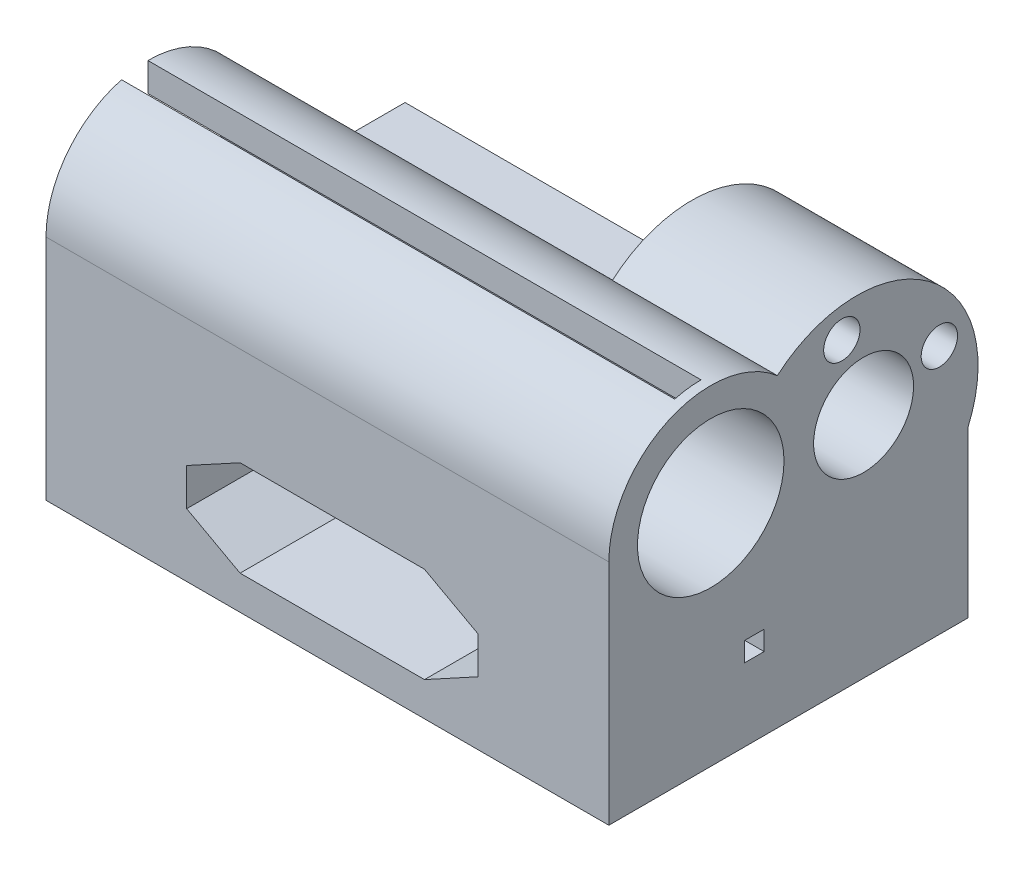
SolidWorks part; units mm, degrees
ref_plane "Front Plane" through (0, 0, 0) normal (0, 0, 1) x (1, 0, 0)
ref_plane "Top Plane" through (0, 0, 0) normal (0, 1, 0) x (1, 0, 0)
ref_plane "Right Plane" through (0, 0, 0) normal (1, 0, 0) x (0, 0, -1)
sketch "Sketch2" plane through (0, 0, 0) normal (0, 1, 0) x (1, 0, 0)
  line L1 (-29, -18.5) -> (29, -18.5)
  line L2 (-29, -18.5) -> (-29, 18.5)
  line L3 (-29, 18.5) -> (29, 18.5)
  line L4 (29, -18.5) -> (29, 18.5)
  line L5 (-29, -18.5) -> (29, 18.5) construction
  line L6 (-29, 18.5) -> (29, -18.5) construction
  point P0 (0, 0)
  dimension "D1" = 58
  dimension "D2" = 37
extrude "Boss-Extrude1" add sketch "Sketch2" along normal blind 17
sketch "Sketch3" plane through (29, 0, 0) normal (1, 0, 0) x (0, 0, -1)
  line L0 (-18.5, 0) -> (18.5, 0) construction
  line L1 (-18.5, 23.5) -> (-18.5, 17)
  line L2 (-18.5, 17) -> (-18.5, 0) construction
  line L5 (2.5, 23.5) -> (2.5, 17)
  line L6 (-18.5, 17) -> (18.5, 17) construction
  line L7 (-18.5, 17) -> (2.5, 17)
  arc A0 (2.5, 23.5) -> (-18.5, 23.5) centre (-8, 23.5) ccw
  dimension "D2" = 21
  dimension "D4" = 23.5
  dimension "D5" = 10.5
extrude "Boss-Extrude2" add sketch "Sketch3" against normal up to surface (58 mm away) up to face at (-29, 8.5, 0)
sketch "Sketch4" plane through (29, 0, 0) normal (1, 0, 0) x (0, 0, -1)
  line L1 (-18.5, 0) -> (18.5, 0) construction
  circle A0 centre (7.0436, 22) radius 12.5
  dimension "D1" = 25
  dimension "D2" = 22
extrude "Boss-Extrude3" add sketch "Sketch4" against normal blind 17
sketch "Sketch5" plane through (0, 0, -18.5) normal (0, 0, -1) x (-1, 0, 0)
  line L0 (-15.5, 6.5) -> (-15.5, 10.35)
  line L1 (-15.5, 10.35) -> (-10, 13.35)
  line L2 (-10, 13.35) -> (9, 13.35)
  line L3 (9, 13.35) -> (14.5, 10.357)
  line L4 (14.5, 10.357) -> (14.5, 6.5)
  line L5 (14.5, 6.5) -> (9, 3.5)
  line L6 (9, 3.5) -> (-10, 3.5)
  line L7 (-10, 3.5) -> (-15.5, 6.5)
  line L8 (-29, 0) -> (29, 0) construction
  line L9 (-29, 17) -> (-29, 0) construction
  line L10 (-23, 5.2045) -> (-23, 14.6536) construction
  line L11 (22, 4.2644) -> (22, 14.6536) construction
  line L12 (-23, 14.6536) -> (22, 14.6536) construction
  line L13 (-0.5, 14.6536) -> (-0.5, 7.909) construction
  line L14 (-29, 8.5) -> (29, 8.5) construction
  line L15 (29, 17) -> (29, 0) construction
  dimension "D1" = 3.85
  dimension "D2" = 3.857
  dimension "D3" = 3
  dimension "D4" = 3
  dimension "D5" = 5.5
  dimension "D6" = 5.5
  dimension "D8" = 5.5
  dimension "D9" = 19
  dimension "D10" = 3.5
  dimension "D11" = 15
  dimension "D12" = 6
  dimension "D13" = 45
extrude "Cut-Extrude1" cut sketch "Sketch5" against normal through all
sketch "Sketch6" plane through (0, 0, -18.5) normal (0, 0, -1) x (-1, 0, 0)
  line L0 (-29, 0) -> (29, 0) construction
  line L1 (-29, 17) -> (-29, 0) construction
  circle A0 centre (-23, 8.5) radius 4.076
  circle A1 centre (22, 8.5) radius 4.076
  dimension "D5" = 8.152
  dimension "D6" = 8.152
  dimension "D1" = 8.5
  dimension "D2" = 8.5
  dimension "D3" = 6
  dimension "D4" = 45
extrude "Cut-Extrude2" cut sketch "Sketch6" against normal blind 23
sketch "Sketch7" plane through (29, 0, 0) normal (1, 0, 0) x (0, 0, -1)
  line L0 (-18.5, 23.5) -> (-18.5, 0) construction
  line L1 (-18.5, 0) -> (18.5, 0) construction
  circle A0 centre (-8, 23.5) radius 7.55
  circle A1 centre (7.7501, 23.5) radius 5.15
  dimension "D1" = 10.3
  dimension "D2" = 15.1
  dimension "D3" = 26.2501
  dimension "D4" = 23.5
extrude "Cut-Extrude3" cut sketch "Sketch7" against normal through all
sketch "Sketch8" plane through (29, 0, 0) normal (1, 0, 0) x (0, 0, -1)
  line L0 (7.7501, 23.5) -> (5.5097, 31.31) construction
  line L3 (7.7501, 23.5) -> (15.5601, 25.7405) construction
  line L4 (5.5097, 31.31) -> (6.0267, 29.5077) construction
  line L7 (15.5601, 25.7405) -> (13.7578, 25.2235) construction
  circle A1 centre (5.5097, 31.31) radius 1.875
  circle A2 centre (15.5601, 25.7405) radius 1.875
  dimension "D1" = 3.75
  dimension "D2" = 6.25
  dimension "D3" = 3.75
  dimension "D7" = 6.25
extrude "Cut-Extrude4" cut sketch "Sketch8" against normal through all
sketch "Sketch12" plane through (-29, 0, 0) normal (-1, 0, 0) x (0, 0, 1)
  line L0 (-18.5, 17) -> (-18.5, 0) construction
  line L1 (4.5, 7.5) -> (2.5, 7.5)
  line L2 (4.5, 7.5) -> (4.5, 9.5)
  line L3 (4.5, 9.5) -> (2.5, 9.5)
  line L4 (2.5, 7.5) -> (2.5, 9.5)
  line L5 (-18.5, 0) -> (18.5, 0) construction
  dimension "D1" = 23
  dimension "D2" = 2
  dimension "D3" = 2
  dimension "D4" = 7.5
extrude "Cut-Extrude6" cut sketch "Sketch12" against normal blind 8
mirror "Mirror1" about plane through (0, 0, 0) normal (1, 0, 0) of "Cut-Extrude6"
sketch "Sketch13" plane through (-29, 0, 0) normal (-1, 0, 0) x (0, 0, 1)
  line L0 (8, 23.5) -> (10.7176, 33.6422) construction
  line L1 (8, 23.5) -> (-2.5, 23.5) construction
  line L2 (8, 23.5) -> (8, 34) construction
  line L3 (9.9541, 30.7927) -> (10.7176, 33.6422)
  line L4 (8, 34) -> (8, 31.05)
  arc A0 (9.9541, 30.7927) -> (8, 31.05) centre (8, 23.5) ccw
  arc A1 (-2.5, 23.5) -> (8, 34) centre (8, 23.5) ccw
  arc A2 (18.5, 23.5) -> (-2.5, 23.5) centre (8, 23.5) ccw construction
  arc A3 (1.1397, 31.449) -> (-2.5, 23.5) centre (8, 23.5) ccw construction
  circle A4 centre (8, 23.5) radius 7.55 construction
  circle M5 centre (8, 23.5) radius 7.55
  arc M8 (18.5, 23.5) -> (-2.5, 23.5) centre (8, 23.5) ccw
  dimension "D1" = 15
  dimension "D2" = 90
extrude "Cut-Extrude7" cut sketch "Sketch13" against normal blind 57 contours L4 L3 M8 M5 region at (-29, 32.5017, 9.1851)
sketch "Sketch14" plane through (0, 0, 0) normal (0, -1, 0) x (1, 0, 0)
  line L0 (0.5, -11.5) -> (29, -11.5) construction
  line L1 (29, 18.5) -> (29, -18.5) construction
  line L2 (0.5, -11.5) -> (0.5, -18.5) construction
  line L3 (29, -18.5) -> (-29, -18.5) construction
  circle A0 centre (0.5, -11.5) radius 1.5
  dimension "D1" = 3
  dimension "D2" = 7
  dimension "D3" = 28.5
extrude "Cut-Extrude8" cut sketch "Sketch14" against normal through all
